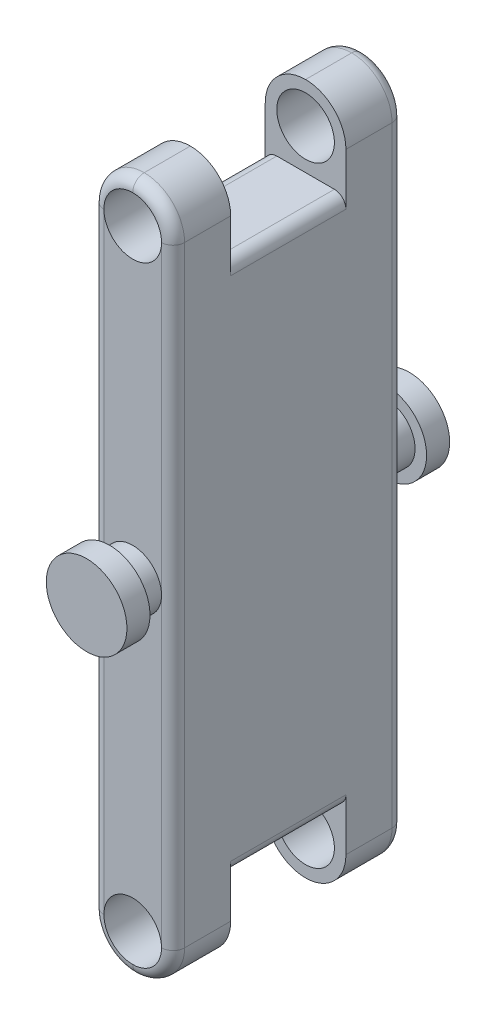
SolidWorks part; units mm, degrees
ref_plane "Front Plane" through (0, 0, 0) normal (0, 0, 1) x (1, 0, 0)
ref_plane "Top Plane" through (0, 0, 0) normal (0, 1, 0) x (1, 0, 0)
ref_plane "Right Plane" through (0, 0, 0) normal (1, 0, 0) x (0, 0, -1)
sketch "Sketch1" plane through (0, 0, 0) normal (0, 1, 0) x (1, 0, 0)
  line L1 (0, 0) -> (14, 0)
  line L2 (0, 0) -> (0, -20)
  line L3 (0, -20) -> (14, -20)
  line L4 (14, 0) -> (14, -20)
  dimension "D1" = 20
  dimension "D2" = 14
extrude "Boss-Extrude1" add sketch "Sketch1" along normal blind 120
sketch "Sketch4" plane through (0, 120, 0) normal (0, 1, 0) x (1, 0, 0)
  line L0 (14, -20) -> (14, 0) construction
  line L1 (0, 0) -> (14, 0)
  line L2 (0, 0) -> (0, -10)
  line L3 (0, -10) -> (14, -10)
  line L4 (14, 0) -> (14, -10)
  dimension "D1" = 10
extrude "Cut-Extrude3" cut sketch "Sketch4" against normal blind 14
sketch "Sketch6" plane through (0, 0, 10) normal (0, 0, -1) x (-1, 0, 0)
  circle A0 centre (-7, 113) radius 5
  dimension "D1" = 10
extrude "Cut-Extrude5" cut sketch "Sketch6" against normal blind 10
mirror "Mirror1" about plane through (0, 120, 0) normal (0, 0, 1) of "Cut-Extrude5", "Cut-Extrude3", "Boss-Extrude1"
sketch "Sketch10" plane through (0, 0, 0) normal (0, -1, 0) x (1, 0, 0)
  line L0 (0, -20) -> (0, 20) construction
  line L1 (0, 10) -> (14, 10)
  line L2 (0, 10) -> (0, -10)
  line L3 (0, -10) -> (14, -10)
  line L4 (14, 10) -> (14, -10)
  line L5 (14, 20) -> (14, -20) construction
  line L6 (0, 20) -> (14, 20) construction
  dimension "D1" = 20
  dimension "D2" = 10
extrude "Cut-Extrude8" cut sketch "Sketch10" against normal blind 14
sketch "Sketch12" plane through (0, 0, 20) normal (0, 0, 1) x (1, 0, 0)
  line L0 (14, 120) -> (14, 0) construction
  line L1 (0, 0) -> (14, 0) construction
  circle A0 centre (7, 60) radius 5
  dimension "D1" = 10
  dimension "D2" = 7
  dimension "D3" = 60
extrude "Boss-Extrude2" add sketch "Sketch12" along normal blind 4
sketch "Sketch13" plane through (0, 0, 24) normal (0, 0, 1) x (1, 0, 0)
  circle A0 centre (7, 60) radius 7
  dimension "D1" = 14
extrude "Boss-Extrude3" add sketch "Sketch13" along normal blind 4
mirror "Mirror3" about plane through (0, 0, 0) normal (0, 0, 1) of "Boss-Extrude3", "Boss-Extrude2"
sketch "Sketch14" plane through (0, 0, 0) normal (0, 0, 1) x (1, 0, 0)
  line L0 (14, 120) -> (14, 0) construction
  line L2 (0, 0) -> (14, 0) construction
  circle A0 centre (7, 7) radius 5
  dimension "D1" = 10
  dimension "D2" = 7
  dimension "D3" = 7
extrude "Cut-Extrude9" cut sketch "Sketch14" against normal through all and the other way through all
fillet "Fillet1" radius 7 8 edges at (14, 0, 15) (0, 0, 15) (14, 0, -15) (0, 0, -15) (14, 120, 15) (0, 120, 15) (14, 120, -15) (0, 120, -15)
fillet "Fillet2" radius 2 16 edges at (11.9497, 117.9497, -20) (2.0503, 117.9497, -20) (0, 60, -20) (2.0503, 2.0503, -20) (11.9497, 2.0503, -20) (11.9497, 117.9497, 20) (2.0503, 117.9497, 20) (0, 60, 20) (2.0503, 2.0503, 20) (11.9497, 2.0503, 20) (14, 14, 0) (0, 14, 0) (14, 60, -20) (14, 60, 20)
